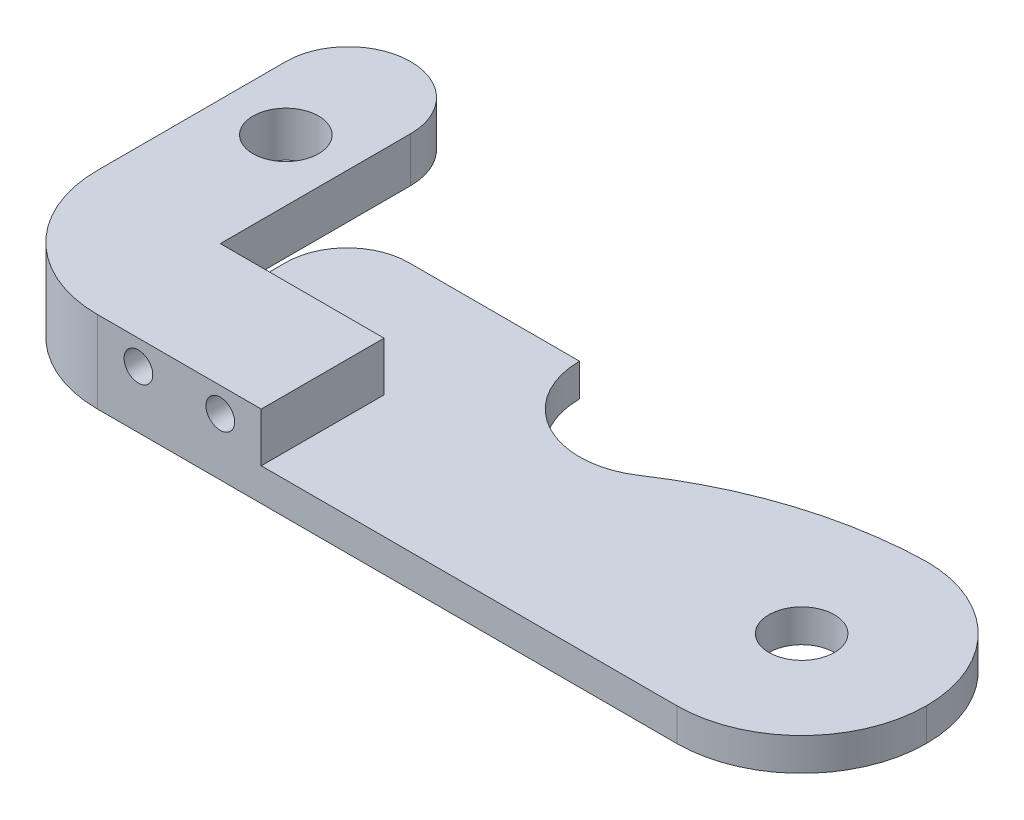
SolidWorks part; units mm, degrees
ref_plane "Front Plane" through (0, 0, 0) normal (0, 0, 1) x (1, 0, 0)
ref_plane "Top Plane" through (0, 0, 0) normal (0, 1, 0) x (1, 0, 0)
ref_plane "Right Plane" through (0, 0, 0) normal (1, 0, 0) x (0, 0, -1)
sketch "Sketch1" plane through (0, 0, 0) normal (0, 1, 0) x (1, 0, 0)
  line L0 (-13.6869, -1.9274) -> (20.7131, -1.9274)
  line L6 (-13.6869, 10.2726) -> (-13.6869, -1.9274)
  line L8 (-13.6869, 10.2726) -> (20.7131, 10.2726)
  line L10 (20.7131, 10.2726) -> (20.7131, -1.9274)
  point P0 (0, 0)
  dimension "D3" = 12.2
  dimension "D1" = 34.4
extrude "Boss-Extrude1" add sketch "Sketch1" along normal blind 1.6
sketch "Sketch8" plane through (0, 1.6, 0) normal (0, 1, 0) x (1, 0, 0)
  line L0 (5.7631, 10.2726) -> (-2.3369, 10.2726)
  line L1 (20.7131, -1.9274) -> (20.7131, 10.2726) construction
  line L2 (20.7131, -1.9274) -> (20.7131, 10.2726) construction
  line L3 (-13.6869, -1.9274) -> (20.7131, -1.9274) construction
  line L4 (20.7131, 10.2726) -> (-13.6869, 10.2726) construction
  line L6 (-13.6869, 10.2726) -> (-13.6869, -1.9274) construction
  circle A0 centre (14.6131, 4.1726) radius 1.6
  arc A1 (-2.3369, 10.2726) -> (5.7631, 10.2726) centre (1.7131, 10.2726) ccw
  dimension "D1" = 3.2
  dimension "D5" = 8.1
  dimension "D2" = 6.1
  dimension "D4" = 6.1
  dimension "D6" = 19
extrude "Cut-Extrude3" cut sketch "Sketch8" against normal through all
fillet "Fillet2" radius 3 1 edges at (-13.6869, 0.8, -10.2726)
fillet "Fillet3" radius 6.1 2 edges at (20.7131, 0.8, 1.9274) (20.7131, 0.8, -10.2726)
sketch "Sketch2" plane through (0, 1.6, 0) normal (0, 1, 0) x (1, 0, 0)
  line L1 (-13.6869, -1.9274) -> (-5.6869, -1.9274)
  line L2 (-13.6869, -1.9274) -> (-13.6869, 4.0726)
  line L3 (-13.6869, 4.0726) -> (-5.6869, 4.0726)
  line L4 (-5.6869, -1.9274) -> (-5.6869, 4.0726)
  dimension "D1" = 8
  dimension "D2" = 6
extrude "Boss-Extrude2" add sketch "Sketch2" along normal blind 2.4
sketch "Sketch3" plane through (0, 0, 1.9274) normal (0, 0, 1) x (1, 0, 0)
  line L0 (-5.6869, 4) -> (-5.6869, 1.6) construction
  line L1 (-13.6869, 4) -> (-5.6869, 4) construction
  line L2 (-13.6869, 4) -> (-5.6869, 4) construction
  circle A0 centre (-11.6869, 2.8) radius 0.7
  circle A1 centre (-7.6869, 2.8) radius 0.7
  dimension "D1" = 1.4
  dimension "D2" = 1.4
  dimension "D3" = 2
  dimension "D4" = 4
  dimension "D5" = 1.2
  dimension "D6" = 1.2
extrude "Cut-Extrude1" cut sketch "Sketch3" against normal up to surface (6 mm away) up to face at (-9.6869, 2.8, -4.0726)
ref_plane "Plane1" through (0, 1.8, 0) normal (0, 1, 0) x (1, 0, 0)
sketch "Sketch4" plane through (0, 0, 0) normal (0, -1, 0) x (1, 0, 0)
  line L0 (-13.6869, 1.9274) -> (-13.6869, -4.1726)
  line L2 (-13.6869, -4.1726) -> (-19.7869, -4.1726)
  arc A0 (-13.6869, 1.9274) -> (-19.7869, -4.1726) centre (-13.6869, -4.1726) ccw
  dimension "D1" = 6.1
extrude "Boss-Extrude3" add sketch "Sketch4" against normal blind 4 separate body
sketch "Sketch5" plane through (0, 0, -4.1726) normal (0, 0, -1) x (-1, 0, 0)
  line L0 (19.7869, 4) -> (19.7869, 0) construction
  line L1 (13.6869, 4) -> (19.7869, 4)
  line L2 (13.6869, 4) -> (13.6869, 1.8)
  line L3 (13.6869, 1.8) -> (19.7869, 1.8)
  line L4 (19.7869, 4) -> (19.7869, 1.8)
extrude "Boss-Extrude4" add sketch "Sketch5" along normal blind 9.2
sketch "Sketch6" plane through (0, 4, 0) normal (0, 1, 0) x (1, 0, 0)
  line L0 (-19.7869, 13.3726) -> (-13.6869, 13.3726) construction
  line L1 (-19.7869, 13.3726) -> (-13.6869, 13.3726)
  arc A0 (-13.6869, 13.3726) -> (-19.7869, 13.3726) centre (-16.7369, 13.3726) ccw
extrude "Boss-Extrude5" add sketch "Sketch6" against normal up to surface (2.2 mm away) up to face at (-16.7369, 1.8, -8.7726)
sketch "Sketch7" plane through (0, 4, 0) normal (0, 1, 0) x (1, 0, 0)
  line L0 (-5.6869, -1.9274) -> (14.6131, -1.9274) construction
  line L2 (-19.7869, 13.3726) -> (-19.7869, 4.1726) construction
  circle A0 centre (-16.6869, 10.2726) radius 1.6
  dimension "D2" = 3.2
  dimension "D1" = 12.2
  dimension "D3" = 3.1
extrude "Cut-Extrude2" cut sketch "Sketch7" against normal up to surface (2.2 mm away) up to face at (-16.7369, 1.8, -9.5351)
fillet "Fillet1" radius 20 1 edges at (5.7631, 0.8, -10.2726)
